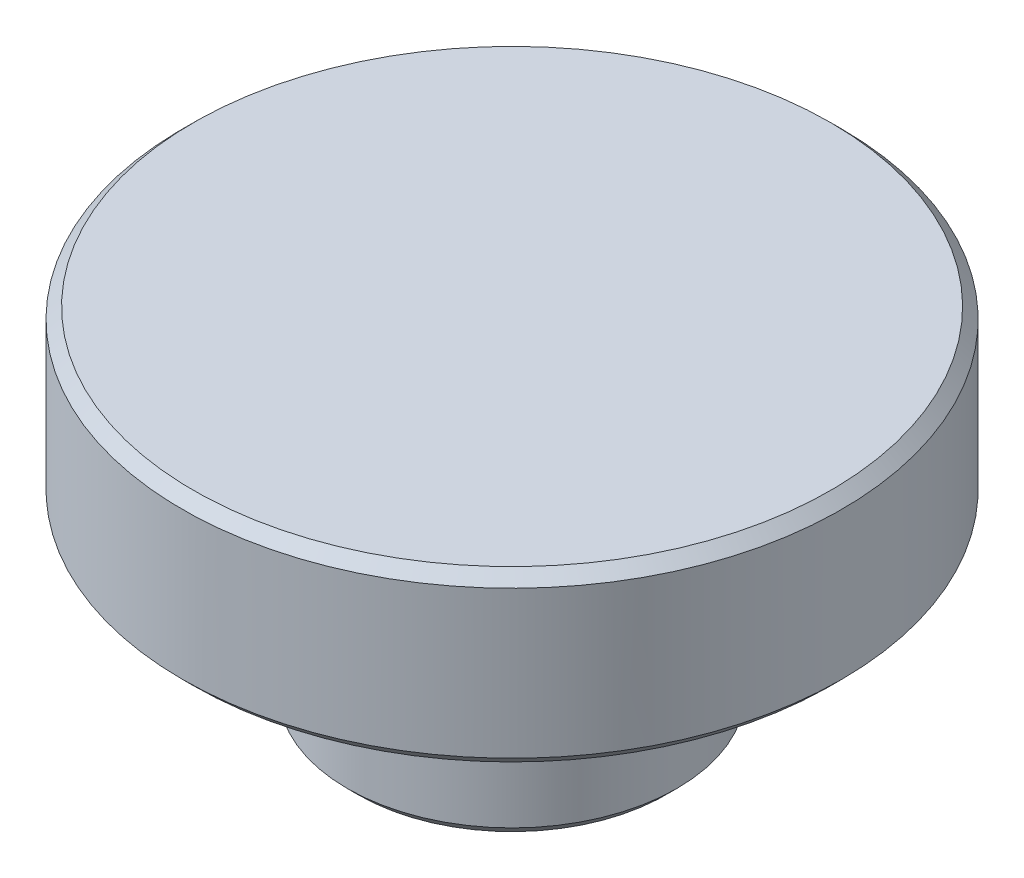
SolidWorks part; units mm, degrees
ref_plane "Front Plane" through (0, 0, 0) normal (0, 0, 1) x (1, 0, 0)
ref_plane "Top Plane" through (0, 0, 0) normal (0, 1, 0) x (1, 0, 0)
ref_plane "Right Plane" through (0, 0, 0) normal (1, 0, 0) x (0, 0, -1)
sketch "Sketch1" plane through (0, 0, 0) normal (0, 0, 1) x (1, 0, 0)
  line L0 (0, 0) -> (0, 17.633) construction
  line L1 (0, 15.75) -> (-15, 15.75)
  line L2 (-15, 15.75) -> (-15, 8.05)
  line L3 (-15, 8.05) -> (-7.5, 8.05)
  line L4 (-7.5, 8.05) -> (-7.5, 0)
  line L5 (-7.5, 0) -> (-2.5, 0)
  line L6 (-2.5, 0) -> (-2.5, 10)
  line L7 (-2.5, 10) -> (0, 10)
  line L8 (0, 10) -> (0, 15.75)
  dimension "D1" = 2.5
  dimension "D2" = 7.5
  dimension "D3" = 15.75
  dimension "D4" = 7.7
  dimension "D5" = 10
  dimension "D6" = 15
revolve "Revolve1" add sketch "Sketch1" angle 360 about L0
chamfer "Chamfer1" distance 0.5 angle 45 4 edges at (0, 0, -7.5) (0, 8.05, -7.5) (0, 8.05, -15) (0, 15.75, -15)
sketch "Sketch2" plane through (0, 0, 0) normal (0, 0, 1) x (1, 0, 0)
  line L0 (-7, 0) -> (7, 0) construction
  circle A0 centre (0, 4.5) radius 1
  dimension "D1" = 2
  dimension "D2" = 4.5
extrude "Cut-Extrude1" cut sketch "Sketch2" against normal through all
ref_axis "Set screw axis" through (0, 4.5, -7.5) along (0, 0, 1)
